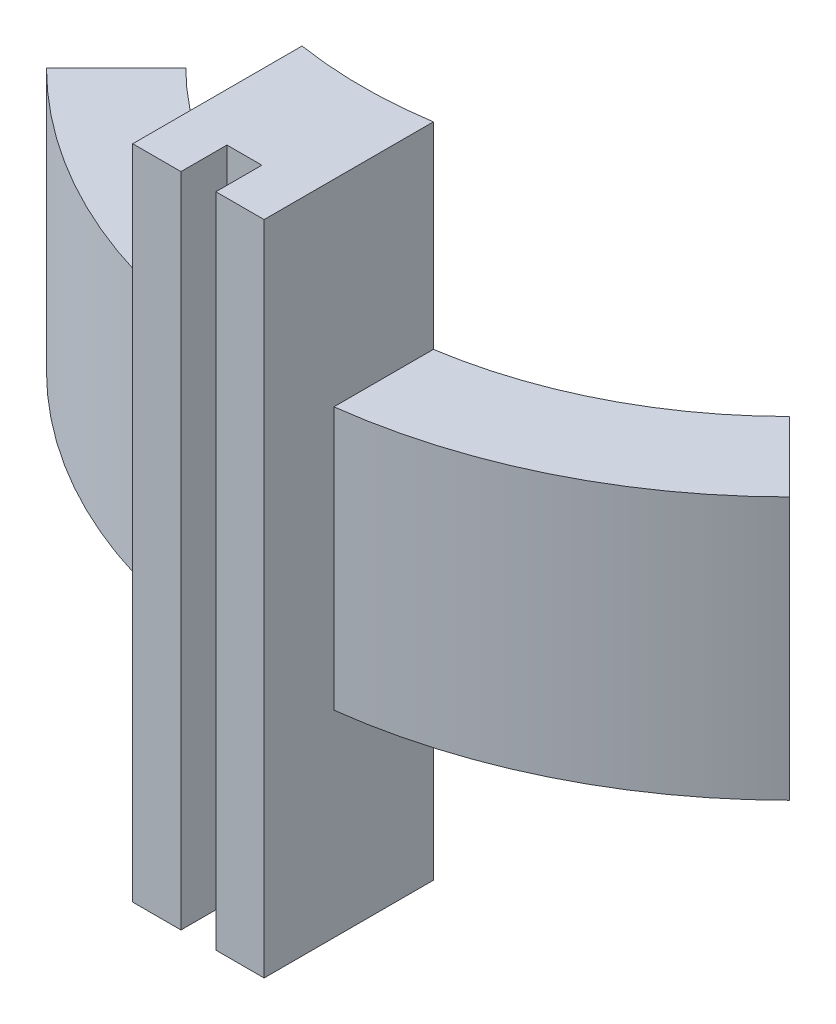
SolidWorks part; units mm, degrees
material "ABS"
ref_plane "Front Plane" through (0, 0, 0) normal (0, 0, 1) x (1, 0, 0)
ref_plane "Top Plane" through (0, 0, 0) normal (0, 1, 0) x (1, 0, 0)
ref_plane "Right Plane" through (0, 0, 0) normal (1, 0, 0) x (0, 0, -1)
sketch "Sketch1" plane through (0, 0, 0) normal (0, 1, 0) x (1, 0, 0)
  line L0 (28.2843, -28.2843) -> (22.981, -22.981)
  line L1 (-28.2843, -28.2843) -> (-22.981, -22.981)
  line L2 (0, -32.5) -> (0, -40)
  line L3 (-22.981, -22.981) -> (0, 0) construction
  line L4 (0, 0) -> (22.981, -22.981) construction
  arc A0 (-28.2843, -28.2843) -> (0, -40) centre (0, 0) ccw
  arc A1 (-22.981, -22.981) -> (0, -32.5) centre (0, 0) ccw
  arc A2 (0, -32.5) -> (22.981, -22.981) centre (0, 0) ccw
  arc A3 (0, -40) -> (28.2843, -28.2843) centre (0, 0) ccw
  point P1 (0, 0)
  point P3 (0, 0)
  dimension "D1" = 7.5
  dimension "D3" = 45
  dimension "D2" = 40
extrude "Boss-Extrude1" add sketch "Sketch1" along normal blind 10 and the other way blind 10 contours L2 A3 L0 A2 | A1 L1 A0 L2 region at (13.5667, 0, 32.7529) region at (-13.5667, 0, 32.7529)
ref_plane "Plane1" through (0, 0, 0) normal (0, 1, 0) x (1, 0, 0)
sketch "Sketch2" plane through (0, 0, 0) normal (0, 1, 0) x (1, 0, 0)
  line L0 (-22.981, -22.981) -> (22.981, -22.981) construction
  line L1 (0, -22.981) -> (0, -32.5) construction
  line L2 (0, -32.5) -> (0, -40) construction
  line L3 (-22.981, -22.981) -> (-35.7598, -35.7598) construction
  line L4 (1.3286, -45) -> (5, -45)
  line L6 (-5, -40) -> (-5, -45)
  line L7 (-5, -45) -> (-1.3286, -45)
  line L8 (5, -40) -> (5, -45)
  line L10 (-1.3286, -45) -> (-1.3286, -41.5)
  line L11 (-1.3286, -41.5) -> (1.3286, -41.5)
  line L12 (1.3286, -45) -> (1.3286, -41.5)
  line L13 (-5, -40) -> (5, -40)
  line L15 (-5, -32.5) -> (5, -32.5)
  line L16 (-5, -32.5) -> (-5, -32.1131)
  line L17 (-5, -32.5) -> (5, -32.5)
  line L18 (-5, -32.5) -> (-5, -40)
  line L19 (-5, -40) -> (5, -40)
  line L20 (5, -32.5) -> (5, -40)
  line L21 (5, -32.5) -> (5, -32.1131)
  arc A0 (-28.2843, -28.2843) -> (28.2843, -28.2843) centre (0, 0) ccw construction
  arc A4 (-22.981, -22.981) -> (22.981, -22.981) centre (0, 0) ccw
  point P14 (0, -32.5)
  point P19 (0, -40)
  point P26 (0, -32.5)
  dimension "D3" = 2.6572
  dimension "D4" = 3.5
extrude "Boss-Extrude2" add sketch "Sketch2" along normal blind 25 and the other way blind 25 contours L6 L7 L10 L11 L12 L4 L8 | L20 L17 L15 L18 L13 | A4 L17 L21 | A4 L16 L15 region at (1.4404, 0, 43.25) region at (0, 0, 36.25) region at (3.7515, 0, 32.384) region at (-3.7515, 0, 32.384)
